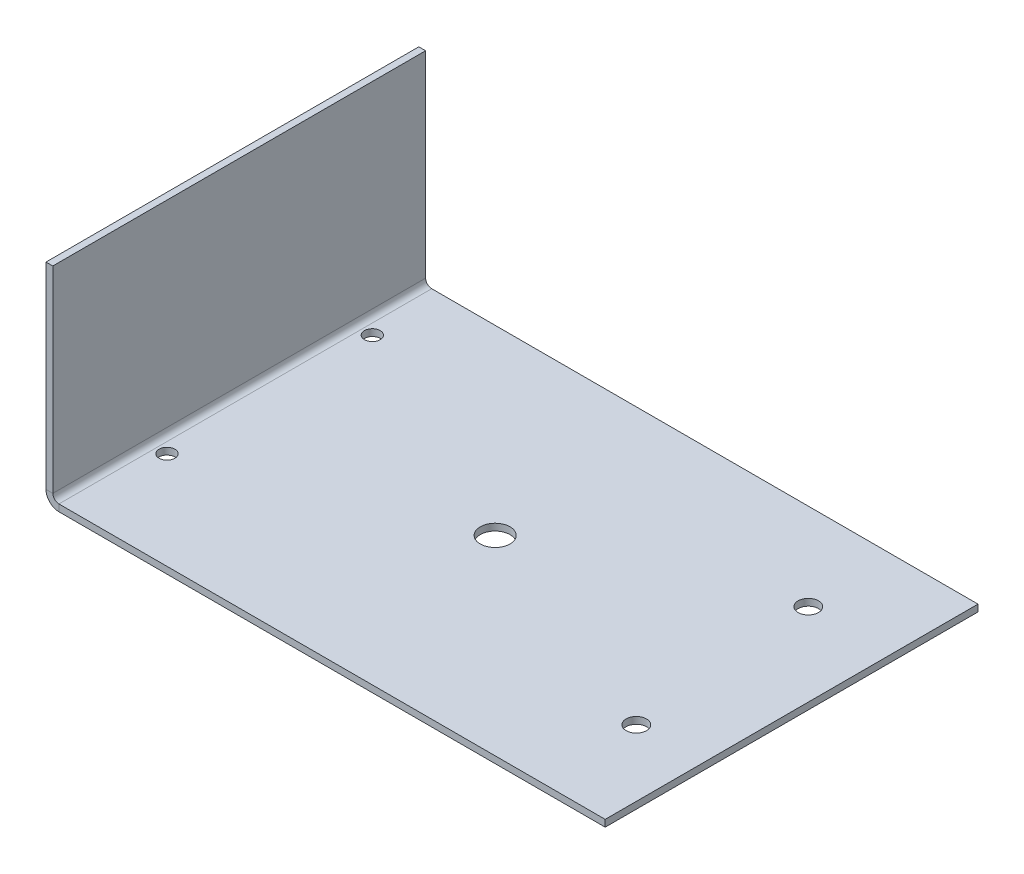
SolidWorks part; units mm, degrees
note: The reader was unsure of these and kept them because the rebuilt part matched: flange length of "Edge-Flange1".
material "Plain Carbon Steel"
ref_plane "Front Plane" through (0, 0, 0) normal (0, 0, 1) x (1, 0, 0)
ref_plane "Top Plane" through (0, 0, 0) normal (0, 1, 0) x (1, 0, 0)
ref_plane "Right Plane" through (0, 0, 0) normal (1, 0, 0) x (0, 0, -1)
sketch "Sketch1" plane through (0, 0, 0) normal (0, 1, 0) x (1, 0, 0)
  line L1 (0, 0) -> (152.4, 0)
  line L2 (0, 0) -> (0, 101.6)
  line L3 (0, 101.6) -> (152.4, 101.6)
  line L4 (152.4, 0) -> (152.4, 101.6)
  line L5 (0, 0) -> (152.4, 101.6) construction
  line L6 (0, 101.6) -> (152.4, 0) construction
  point P4 (76.2, 50.8)
  dimension "D1" = 101.6
  dimension "6" = 152.4
base flange "Base-Flange1" sketch "Sketch1" thickness 1.8542 reverse thickness direction no parameters "D1"=1.6637
edge flange "Edge-Flange1" sketch "Sketch8" flange angle 90 flange length 57.1881 flange position material inside bend radius 1.6637 thickness 1.8542 relief rectangular parameters "D6"=10
sketch "Sketch8" plane through (0, 0, 0) normal (-1, 0, 0) x (0, 0, 1)
  line L0 (-101.6, 0) -> (0, 0) construction
  line L1 (-101.6, 0) -> (0, 0)
  line L2 (-101.6, 0) -> (-101.6, 55.3339)
  line L3 (-101.6, 55.3339) -> (0, 55.3339)
  line L4 (0, 55.3339) -> (0, 0)
bend "EdgeBend1" bend radius 1.6637 bend angle 90 parameters "D5"=1
hole_wizard "1/4-20 Tapped Hole1" positions "Sketch9" profile "Sketch10" tap size "1/4-20" standard "ANSI Inch" end condition through all
sketch "Sketch9" plane through (0, 0, 0) normal (0, 1, 0) x (1, 0, 0)
  point P0 (129.8782, 77.8709)
  point P2 (134.3222, 26.5607)
sketch "Sketch10" plane through (129.8782, 0, -77.8709) normal (1, 0, 0) x (0, 0, 1)
  line L0 (0, 0) -> (0, 1.8542)
  line L1 (0, 1.8542) -> (2.7788, 1.8542)
  line L2 (2.7788, 1.8542) -> (2.7788, 0)
  line L5 (2.7788, 0) -> (0, 0)
  line L11 (0, -6.35) -> (0, 107.95) construction
  dimension "Thru Tap Drill Dia." = 5.5575
  dimension "Thru Tap Drill Depth" = 1.8542
cosmetic thread "Hole Thread1"
cosmetic thread "Hole Thread2"
hole_wizard "3/8-16 Tapped Hole1" positions "Sketch11" profile "Sketch12" tap size "3/8-16" standard "ANSI Inch" end condition through all
sketch "Sketch11" plane through (0, 0, 0) normal (0, 1, 0) x (1, 0, 0)
  point P0 (70.3804, 52.0253)
sketch "Sketch12" plane through (70.3804, 0, -52.0253) normal (1, 0, 0) x (0, 0, 1)
  line L0 (0, 0) -> (0, 1.8542)
  line L1 (0, 1.8542) -> (4.0576, 1.8542)
  line L2 (4.0576, 1.8542) -> (4.0577, 0)
  line L5 (4.0577, 0) -> (0, 0)
  line L11 (0, -6.35) -> (0, 107.95) construction
  dimension "Thru Tap Drill Dia." = 8.1153
  dimension "Thru Tap Drill Depth" = 1.8542
cosmetic thread "Hole Thread3"
hole_wizard "#10-32 Tapped Hole1" positions "3DSketch1" profile "Sketch13" tap size "#10-32" standard "ANSI Inch" end condition through all
sketch3d "3DSketch1"
  point P0 (6.3831, 0, -26.5806)
  point P2 (6.3884, 0, -82.5513)
sketch "Sketch13" plane through (6.3831, 0, -26.5806) normal (1, 0, 0) x (0, 0, 1)
  line L0 (0, 0) -> (0, 1.8542)
  line L1 (0, 1.8542) -> (2.1526, 1.8542)
  line L2 (2.1526, 1.8542) -> (2.1526, 0)
  line L5 (2.1526, 0) -> (0, 0)
  line L11 (0, -6.35) -> (0, 107.95) construction
  dimension "Thru Tap Drill Dia." = 4.3053
  dimension "Thru Tap Drill Depth" = 1.8542
cosmetic thread "Hole Thread4"
cosmetic thread "Hole Thread5"
sketch "Bend-Lines1" [suppressed] plane through (0, 0, 0) normal (0, 1, 0) x (1, 0, 0)
sketch "Bounding-Box1" [suppressed] plane through (0, 0, 0) normal (0, 1, 0) x (1, 0, 0)
sheet metal parameters "Sheet-Metal6" thickness 1.8542 parameters "D1"=1.6637
flat pattern "Flat-Pattern6" [suppressed]
sketch "Bend-Lines2" plane through (0, 0, 0) normal (0, 1, 0) x (1, 0, 0)
sketch "Bounding-Box2" [suppressed] plane through (0, 0, 0) normal (0, 1, 0) x (1, 0, 0)
sheet metal parameters "Sheet-Metal7" thickness 1.8542 parameters "D1"=1.6637
flat pattern "Flat-Pattern6" [suppressed]
sketch "Bend-Lines2" plane through (0, 0, 0) normal (0, 1, 0) x (1, 0, 0)
sketch "Bounding-Box2" [suppressed] plane through (0, 0, 0) normal (0, 1, 0) x (1, 0, 0)
bend of the flat pattern "Flatten-<EdgeBend1>1"
sheet metal parameters "Sheet-Metal8" thickness 1.8542 parameters "D1"=1.6637
flat pattern "Flat-Pattern6" [suppressed]
sketch "Bend-Lines2" plane through (0, 0, 0) normal (0, 1, 0) x (1, 0, 0)
sketch "Bounding-Box2" [suppressed] plane through (0, 0, 0) normal (0, 1, 0) x (1, 0, 0)
bend of the flat pattern "Flatten-<EdgeBend1>1"
sheet metal parameters "Sheet-Metal9" thickness 1.8542 parameters "D1"=1.6637
flat pattern "Flat-Pattern6" [suppressed]
sketch "Bend-Lines2" plane through (0, 0, 0) normal (0, 1, 0) x (1, 0, 0)
sketch "Bounding-Box2" [suppressed] plane through (0, 0, 0) normal (0, 1, 0) x (1, 0, 0)
bend of the flat pattern "Flatten-<EdgeBend1>1"
sheet metal parameters "Sheet-Metal10" thickness 1.8542 parameters "D1"=1.6637
flat pattern "Flat-Pattern6"
sketch "Bend-Lines2" plane through (0, 0, 0) normal (0, 1, 0) x (1, 0, 0)
  line L0 (1.6628, 101.6) -> (1.6628, 0) construction
  line L1 (1.6628, 101.6) -> (1.6628, 0) construction
sketch3d "Bounding-Box2" [suppressed]
  line L0 (152.4, 101.6, 0) -> (-53.8625, 101.6, 0) construction
  line L1 (152.4, 0, 0) -> (-53.8625, 0, 0) construction
  line L2 (152.4, 101.6, 0) -> (152.4, 0, 0) construction
  line L3 (-53.8625, 101.6, 0) -> (-53.8625, 0, 0) construction
bend of the flat pattern "Flatten-<EdgeBend1>1"
